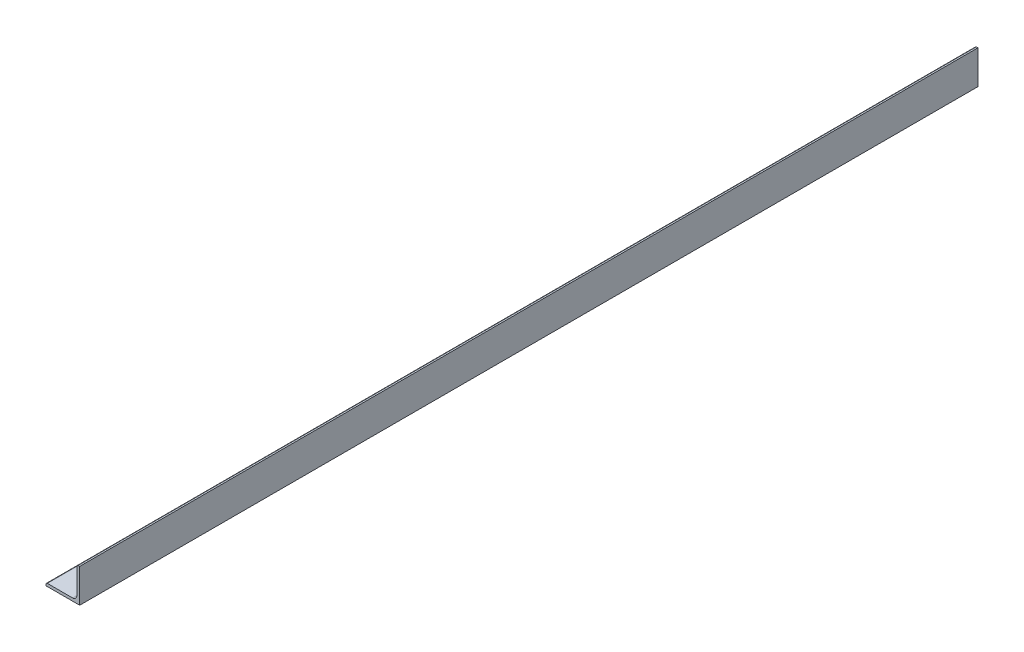
SolidWorks part; units mm, degrees
ref_plane "Front Plane" through (0, 0, 0) normal (0, 0, 1) x (1, 0, 0)
ref_plane "Top Plane" through (0, 0, 0) normal (0, 1, 0) x (1, 0, 0)
ref_plane "Right Plane" through (0, 0, 0) normal (1, 0, 0) x (0, 0, -1)
sketch "Sketch0" plane through (0, 0, 0) normal (0, 0, 1) x (1, 0, 0)
  line L0 (-9.525, -9.525) -> (9.525, -9.525)
  line L1 (9.525, -9.525) -> (9.525, 9.525)
  line L2 (9.525, 0) -> (0, 0) construction
  line L3 (0, 0) -> (0, -9.525) construction
  line L4 (7.9375, -5.5499) -> (7.9375, 9.525) construction
  line L5 (5.5499, -7.9375) -> (-9.525, -7.9375) construction
  arc A0 (7.9375, -5.5499) -> (5.5499, -7.9375) centre (5.5499, -5.5499) cw
  point P3 (7.2382, -7.2382)
  dimension "Inside Corner Radius" = 2.3876
  dimension "Outside Height" = 19.05
  dimension "Inside Height" = 17.4625
  dimension "Inside Width" = 17.4625
  dimension "Wall Thickness" = 1.5875
  dimension "D1" = 1.5875
  dimension "Outside Width" = 19.05
sketch "Sketch1" plane through (0, 0, 0) normal (1, 0, 0) x (0, 0, -1)
  line L0 (254, 0) -> (-254, 0)
  point P4 (0, 0)
  dimension "Length" = 508
sketch "Sketch2" plane through (0, 0, 0) normal (0, 0, 1) x (1, 0, 0)
  line L0 (-9.525, -9.525) -> (9.525, -9.525)
  line L1 (9.525, -9.525) -> (9.525, 9.525)
  line L2 (9.525, 9.525) -> (7.9375, 9.525) construction
  line L3 (7.9375, 8.7313) -> (7.9375, -5.5499)
  line L4 (5.5499, -7.9375) -> (-8.7313, -7.9375)
  line L5 (-9.525, -9.525) -> (-9.525, -7.9375) construction
  line L6 (8.7313, 9.525) -> (9.525, 9.525)
  line L7 (-9.525, -8.7313) -> (-9.525, -9.525)
  line L8 (9.525, 0) -> (0, 0) construction
  line L9 (0, 0) -> (0, -9.525) construction
  arc A0 (7.9375, 8.7313) -> (8.7313, 9.525) centre (8.7313, 8.7313) cw
  arc A1 (-9.525, -8.7313) -> (-8.7313, -7.9375) centre (-8.7313, -8.7313) cw
  arc A2 (7.9375, -5.5499) -> (5.5499, -7.9375) centre (5.5499, -5.5499) cw
  dimension "Inside Radius" = 2.3876
  dimension "Height" = 19.05
  dimension "Width" = 19.05
  dimension "Thickness" = 1.5875
extrude "Boss-Extrude1" add sketch "Sketch2" along normal mid plane 508
sketch "Break Locations" plane through (0, 0, 0) normal (1, 0, 0) x (0, 0, -1)
  line L0 (-234.569, 0) -> (234.569, 0)
  line L1 (-254, -9.525) -> (-254, 9.525) construction
  line L2 (254, -9.525) -> (254, 9.525) construction
  point P0 (-237.8075, 0)
  point P1 (237.8075, 0)
  point P10 (0, 0)
  point P11 (234.569, 0)
  point P13 (-234.569, 0)
  dimension "D1" = 16.1925
  dimension "D2" = 16.1925
  dimension "D3" = 19.431
hole_wizard "#10 Clearance Hole1" positions "Sketch3" profile "Sketch4" hole size "#10" standard "ANSI Inch"
sketch "Sketch3" plane through (0, -9.525, 0) normal (0, -1, 0) x (-1, 0, 0)
  point P2 (-3.1368, 241.3)
  point P5 (-3.1368, 215.9)
  point P8 (-3.175, -241.2618)
  point P11 (-3.175, -215.8618)
sketch "Sketch4" plane through (3.1368, -9.525, -241.3) normal (1, 0, 0) x (0, 0, -1)
  line L0 (0, 0) -> (0, 4.7977)
  line L1 (0, 4.7977) -> (2.4892, 3.302)
  line L2 (2.4892, 3.302) -> (2.4892, 0)
  line L5 (2.4892, 0) -> (0, 0)
  line L10 (0, 4.7977) -> (-2.4892, 3.302) construction
  line L11 (0, -6.35) -> (0, 107.95) construction
  dimension "Hole Dia." = 4.9784
  dimension "Hole Depth" = 3.302
  dimension "Drill Angle" = 118
equation "\"D1@Break Locations\" = .85 * \"Height@Sketch2\""
equation "\"D2@Break Locations\"=\"D1@Break Locations\""
equation "\"Thickness@Sketch2\"=\"wall thickness@sketch0\""
equation "\"Height@Sketch2\"=\"outside height@sketch0\""
equation "\"Width@Sketch2\"=\"outside width@sketch0\""
equation "\"Inside Radius@Sketch2\"=\"inside corner radius@sketch0\""
equation "\"Length@Boss-Extrude1\"=\"length@sketch1\""
equation "\"D3@Break Locations\"=\"D2@Break Locations\"*1.2"
equation "\"D1@Sketch0\"=\"Wall Thickness@Sketch0\""
